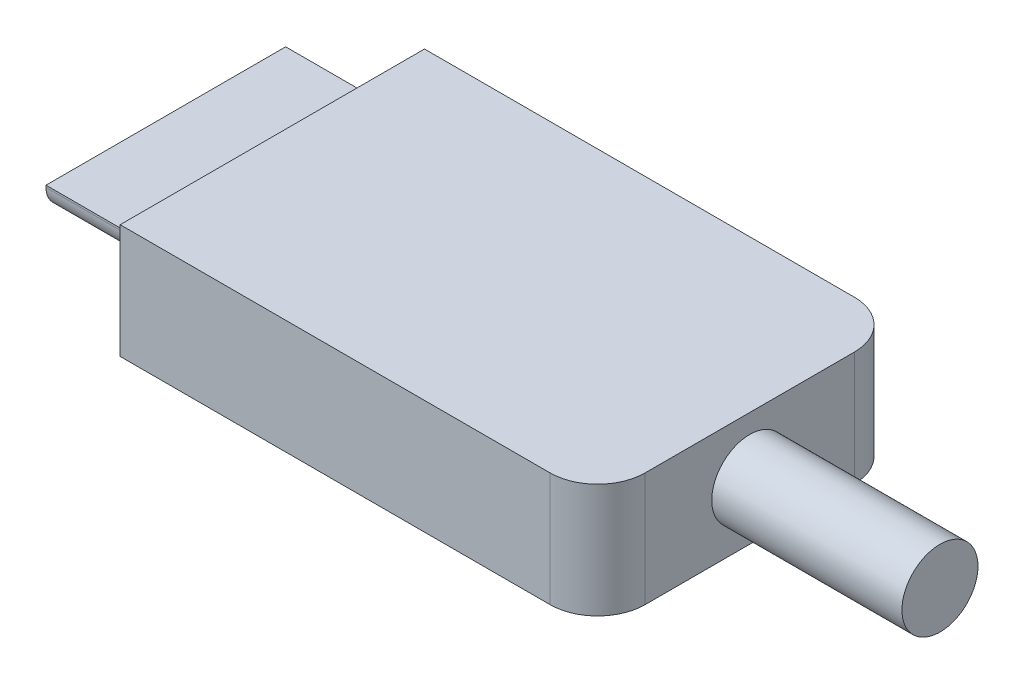
SolidWorks part; units mm, degrees
ref_plane "Front Plane" through (0, 0, 0) normal (0, 0, 1) x (1, 0, 0)
ref_plane "Top Plane" through (0, 0, 0) normal (0, 1, 0) x (1, 0, 0)
ref_plane "Right Plane" through (0, 0, 0) normal (1, 0, 0) x (0, 0, -1)
sketch "Sketch1" plane through (0, 0, 0) normal (0, 1, 0) x (1, 0, 0)
  line L0 (-12.55, 8) -> (12.55, -8) construction
  line L1 (-12.55, 8) -> (10.05, 8)
  line L2 (-12.55, 8) -> (-12.55, -8)
  line L3 (-12.55, -8) -> (10.05, -8)
  line L4 (12.55, 5.5) -> (12.55, -5.5)
  line L5 (10.05, -8) -> (12.55, -8) construction
  line L6 (12.55, -8) -> (12.55, -5.5) construction
  arc A0 (10.05, -8) -> (12.55, -5.5) centre (10.05, -5.5) ccw
  arc A1 (10.05, 8) -> (12.55, 5.5) centre (10.05, 5.5) cw
  dimension "D1" = 2.5
  dimension "D2" = 16
  dimension "D3" = 25.1
extrude "Boss-Extrude1" add sketch "Sketch1" along normal blind 3 and the other way blind 3
sketch "Sketch2" plane through (-12.55, 0, 0) normal (-1, 0, 0) x (0, 0, 1)
  line L29 (0, 0) -> (0, 6.1928) construction
  line L30 (-0.2186, -1.0814) -> (-0.9598, -0.3402) construction
  line L31 (6.7, 1.0446) -> (6.7, 1.175) construction
  line L32 (0.9127, -1.55) -> (4.1054, -1.55) construction
  line L33 (5.2367, -1.0814) -> (6.2314, -0.0867) construction
  line L34 (-1.6, -1.175) -> (-1.6, -0.6053) construction
  line L35 (-6.325, -1.55) -> (-1.975, -1.55) construction
  line L36 (-6.7, 1.175) -> (-6.7, -1.175) construction
  line L37 (6.325, 1.55) -> (-6.325, 1.55) construction
  line L38 (6.7, 1.55) -> (-6.7, -1.55) construction
  line L39 (6.7, 1.55) -> (6.7, 1.175) construction
  line L40 (6.325, 1.55) -> (6.7, 1.55) construction
  line L41 (-6.7, -1.55) -> (-6.325, -1.55) construction
  line L42 (-6.7, -1.175) -> (-6.7, -1.55) construction
  line L43 (4.8125, -0.6571) -> (5.8071, 0.3375)
  line L44 (0.9127, -0.95) -> (4.1054, -0.95)
  line L45 (0.2056, -0.6571) -> (-0.5356, 0.0841)
  line L46 (-2.2, -0.95) -> (-2.2, -0.6053)
  line L47 (-6.1, -0.95) -> (-2.2, -0.95)
  line L48 (-6.1, 0.95) -> (-6.1, -0.95)
  line L49 (6.0955, 0.95) -> (-6.1, 0.95)
  line L50 (6.3, 1.0446) -> (6.3, 1.15)
  line L51 (4.9539, -0.7985) -> (5.9485, 0.1961)
  line L52 (0.9127, -1.15) -> (4.1054, -1.15)
  line L53 (0.0642, -0.7985) -> (-0.677, -0.0573)
  line L54 (-2, -1.15) -> (-2, -0.6053)
  line L55 (-6.3, -1.15) -> (-2, -1.15)
  line L56 (-6.3, 1.15) -> (-6.3, -1.15)
  line L57 (6.3, 1.15) -> (-6.3, 1.15)
  arc A24 (-6.7, 1.175) -> (-6.325, 1.55) centre (-6.325, 1.175) cw construction
  arc A25 (-6.325, -1.55) -> (-6.7, -1.175) centre (-6.325, -1.175) cw construction
  arc A26 (-1.6, -1.175) -> (-1.975, -1.55) centre (-1.975, -1.175) cw construction
  arc A27 (-1.6, -0.6053) -> (-0.9598, -0.3402) centre (-1.225, -0.6053) cw construction
  arc A28 (0.9127, -1.55) -> (-0.2186, -1.0814) centre (0.9127, 0.05) cw construction
  arc A29 (5.2367, -1.0814) -> (4.1054, -1.55) centre (4.1054, 0.05) cw construction
  arc A30 (6.325, 1.55) -> (6.7, 1.175) centre (6.325, 1.175) cw construction
  arc A31 (6.7, 1.0446) -> (6.2314, -0.0867) centre (5.1, 1.0446) cw construction
  arc A32 (6.0955, 0.95) -> (5.8071, 0.3375) centre (5.1, 1.0446) cw
  arc A33 (4.8125, -0.6571) -> (4.1054, -0.95) centre (4.1054, 0.05) cw
  arc A34 (0.9127, -0.95) -> (0.2056, -0.6571) centre (0.9127, 0.05) cw
  arc A35 (-2.2, -0.6053) -> (-0.5356, 0.0841) centre (-1.225, -0.6053) cw
  arc A36 (6.3, 1.0446) -> (5.9485, 0.1961) centre (5.1, 1.0446) cw
  arc A37 (4.9539, -0.7985) -> (4.1054, -1.15) centre (4.1054, 0.05) cw
  arc A38 (0.9127, -1.15) -> (0.0642, -0.7985) centre (0.9127, 0.05) cw
  arc A39 (-2, -0.6053) -> (-0.677, -0.0573) centre (-1.225, -0.6053) cw
extrude "Boss-Extrude2" add sketch "Sketch2" along normal blind 5.6
sketch "Sketch3" plane through (12.55, 0, 0) normal (1, 0, 0) x (0, 0, -1)
  circle A0 centre (0, 0) radius 2
  dimension "D1" = 4
extrude "Boss-Extrude3" add sketch "Sketch3" along normal blind 10
